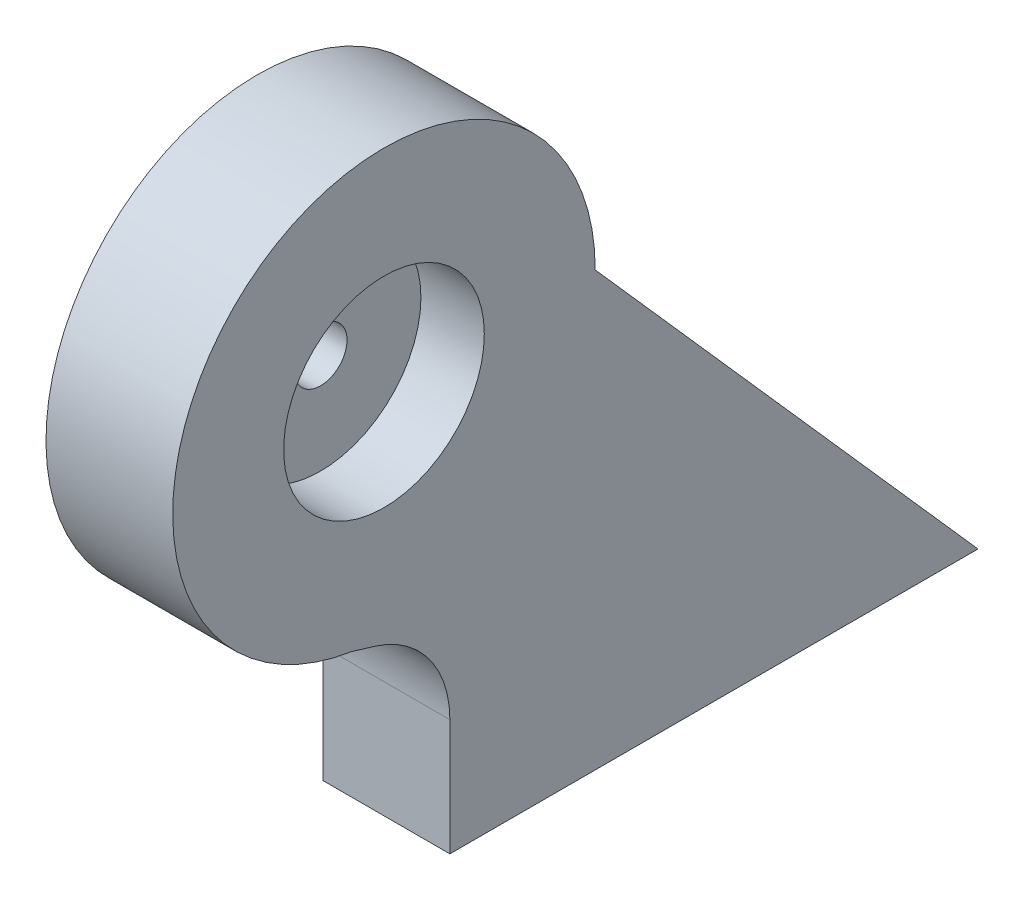
SolidWorks part; units mm, degrees
ref_plane "Front Plane" through (0, 0, 0) normal (0, 0, 1) x (1, 0, 0)
ref_plane "Top Plane" through (0, 0, 0) normal (0, 1, 0) x (1, 0, 0)
ref_plane "Right Plane" through (0, 0, 0) normal (1, 0, 0) x (0, 0, -1)
sketch "Sketch1" plane through (0, 0, 0) normal (1, 0, 0) x (0, 0, -1)
  line L15 (6.2402, -41) -> (56.2402, -41)
  line L36 (20, 0) -> (56.2402, -41)
  line L37 (6.2402, -29.9966) -> (6.2402, -41)
  line L38 (-3.0498, -19.7661) -> (-0.8733, -20.4223)
  line L39 (-3.0498, -19.7661) -> (6.2402, -22.5669)
  arc A2 (20, 0) -> (-3.0498, -19.7661) centre (0, 0) ccw
  circle A3 centre (0, 0) radius 9.5
  circle A14 centre (0, 0) radius 2.5
  arc A15 (6.2402, -29.9966) -> (-0.8733, -20.4223) centre (-3.7598, -29.9966) ccw
  point P6 (1.0168, -0.1839)
  point P26 (0, 0)
  dimension "D1" = 50
  dimension "D5" = 40
  dimension "D7" = 41
  dimension "D8" = 19
  dimension "D6" = 5
  dimension "D4" = 10
  dimension "D2" = 2.8008
  dimension "D3" = 18.4331
extrude "Boss-Extrude1" add sketch "Sketch1" against normal blind 12 contours L38 A15 L37 L15 L36 A2
extrude "Cut-Extrude2" cut sketch "Sketch1<9>" against normal blind 6 contours A3
sketch "Sketch1<9>" plane through (0, 0, 0) normal (1, 0, 0) x (0, 0, -1) same geometry as "Sketch1"
extrude "Cut-Extrude3" cut sketch "Sketch1<10>" against normal up to surface (12 mm away) contours A14 up to face at (-12, -20.9905, -10.8145)
sketch "Sketch1<10>" plane through (0, 0, 0) normal (1, 0, 0) x (0, 0, -1) same geometry as "Sketch1"
sketch "Sketch2" plane through (0, -41, 0) normal (0, -1, 0) x (1, 0, 0)
  line L0 (-6, -6.2402) -> (-6, -19.9702) construction
  line L1 (-12, -6.2402) -> (0, -6.2402) construction
  line L2 (-6, -19.9702) -> (-6, -29.9702) construction
  circle A0 centre (-6, -19.9702) radius 1.52
  circle A1 centre (-6, -29.9702) radius 1.52
  circle A2 centre (-6, -39.9702) radius 1.52
  circle A3 centre (-6, -49.9702) radius 1.52
  dimension "D2" = 3.04
  dimension "D1" = 13.73
  dimension "D3" = 4
  dimension "D4" = 10
extrude "Cut-Extrude4" cut sketch "Sketch2" against normal blind 10
